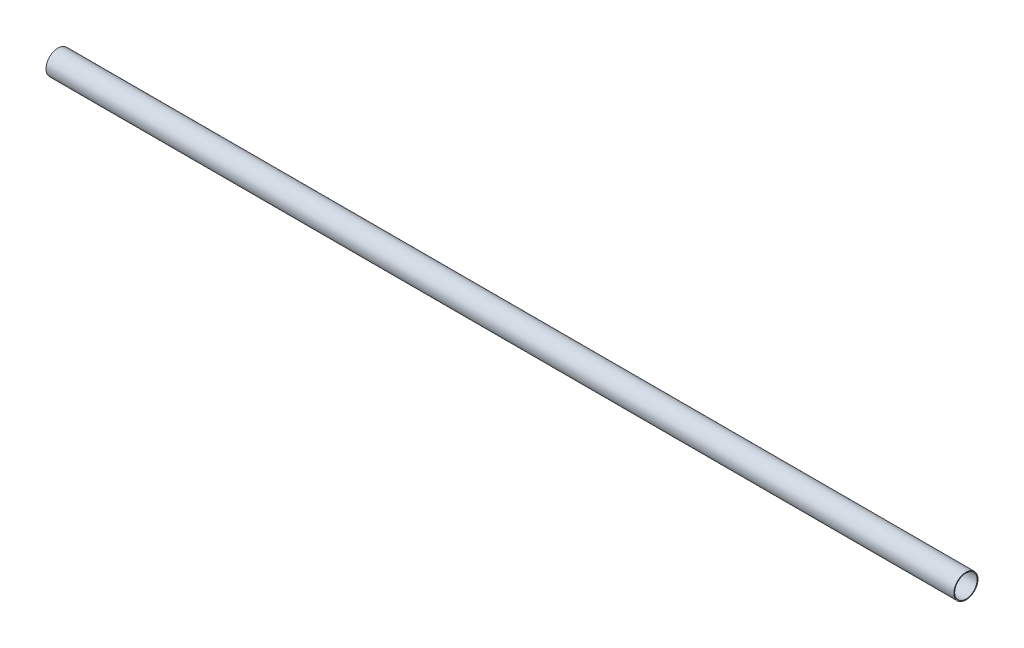
SolidWorks part; units mm, degrees
ref_plane "Front Plane" through (0, 0, 0) normal (0, 0, 1) x (1, 0, 0)
ref_plane "Top Plane" through (0, 0, 0) normal (0, 1, 0) x (1, 0, 0)
ref_plane "Right Plane" through (0, 0, 0) normal (1, 0, 0) x (0, 0, -1)
sketch "Sketch1" plane through (0, 0, 0) normal (1, 0, 0) x (0, 0, -1)
  circle A0 centre (0, 0) radius 12.7
  circle A1 centre (0, 0) radius 11.811
extrude "Boss-Extrude1" add sketch "Sketch1" along normal blind 955
